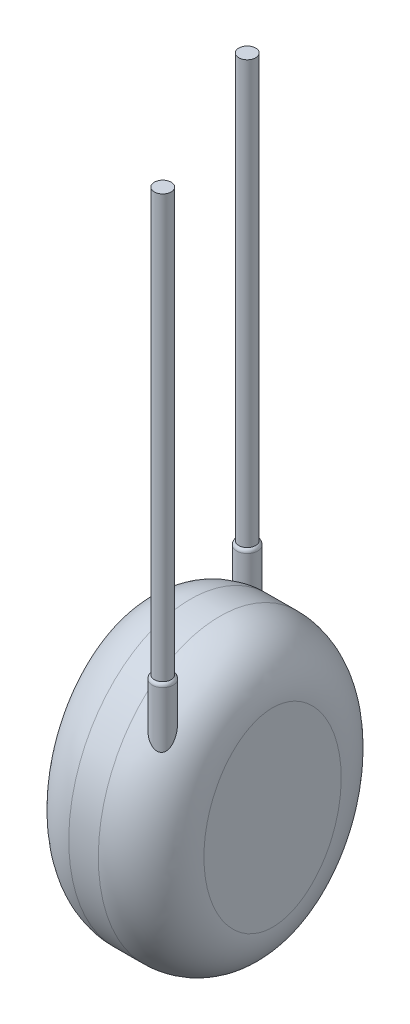
SolidWorks part; units mm, degrees
ref_plane "Alzado" through (0, 0, 0) normal (0, 0, 1) x (1, 0, 0)
ref_plane "Planta" through (0, 0, 0) normal (0, 1, 0) x (1, 0, 0)
ref_plane "Vista lateral" through (0, 0, 0) normal (1, 0, 0) x (0, 0, -1)
sketch "Croquis1" plane through (0, 0, 0) normal (1, 0, 0) x (0, 0, -1)
  ellipse E0 centre (0, 0) end of major axis (0, 7) minor radius 5.75
  dimension "D1" = 14
extrude "Saliente-Extruir1" add sketch "Croquis1" along normal blind 6.4
ref_plane "Plano1" through (0, 7, 0) normal (0, -1, 0) x (-1, 0, 0)
sketch "Croquis2" plane through (0, 7, 0) normal (0, -1, 0) x (-1, 0, 0)
  line L0 (-11.4458, 0) -> (12.5467, 0) construction
  line L1 (-3.2, -4.5026) -> (-3.2, -6.9974) construction
  line L3 (-6.4, -5.75) -> (0, -5.75) construction
  line L4 (0, -5.75) -> (-6.4, -5.75) construction
  circle A0 centre (-1.45, 3.75) radius 0.5
  circle A1 centre (-4.95, -3.75) radius 0.5
  point P14 (-3.2, -5.75)
  dimension "D5" = 1
  dimension "D1" = 3.75
  dimension "D2" = 3.75
  dimension "D3" = 1.75
  dimension "D4" = 1.75
  dimension "D6" = 6.4
extrude "Saliente-Extruir2" add sketch "Croquis2" along normal up to surface (1.6935 mm away) up to face at (6.4, 7, 0)
sketch "Croquis3" plane through (0, 7, 0) normal (0, 1, 0) x (1, 0, 0)
  circle A0 centre (4.95, -3.75) radius 0.4
  circle A1 centre (1.45, 3.75) radius 0.4
  dimension "D1" = 0.8
extrude "Saliente-Extruir3" add sketch "Croquis3" along normal blind 20
fillet "Redondeo1" radius 0.2 2 edges at (1.95, 7, -3.75) (5.45, 7, 3.75)
fillet "Redondeo2" radius 2.5 2 edges at (0, 7, 0) (6.4, 7, 0)
